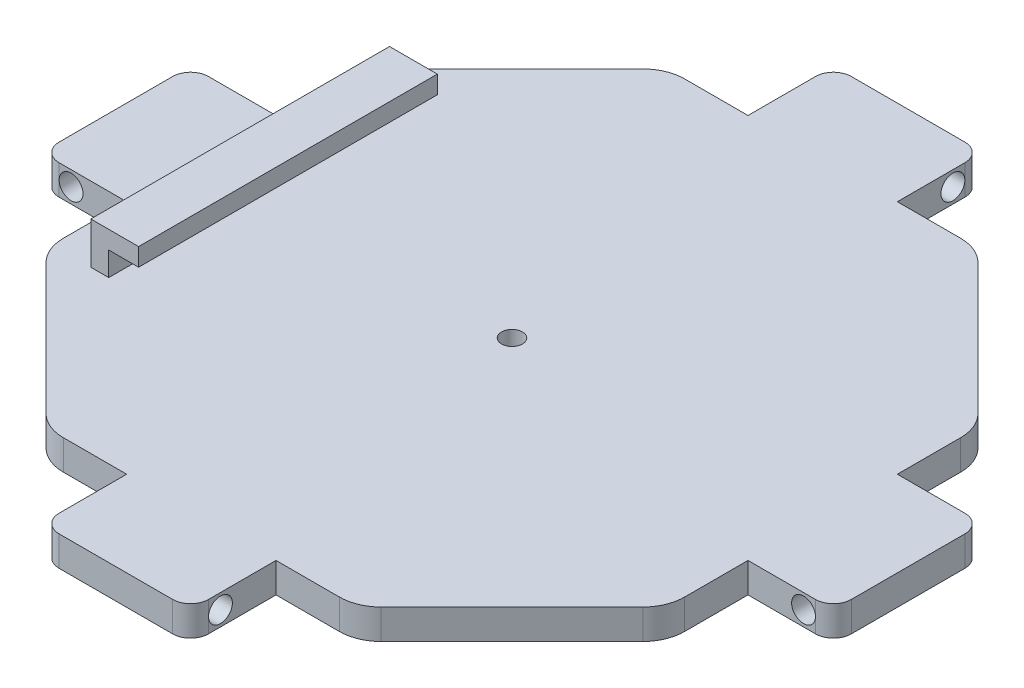
SolidWorks part; units mm, degrees
ref_plane "정면" through (0, 0, 0) normal (0, 0, 1) x (1, 0, 0)
ref_plane "윗면" through (0, 0, 0) normal (0, 1, 0) x (1, 0, 0)
ref_plane "우측면" through (0, 0, 0) normal (1, 0, 0) x (0, 0, -1)
sketch "스케치1" plane through (0, 0, 0) normal (0, 1, 0) x (1, 0, 0)
  line L0 (0, 0) -> (-27.1519, 0) construction
  line L1 (-39, 39) -> (39, 39)
  line L2 (-39, 39) -> (-39, -39)
  line L3 (-39, -39) -> (39, -39)
  line L4 (39, 39) -> (39, -39)
  line L5 (-39, 39) -> (39, -39) construction
  line L6 (-39, -39) -> (39, 39) construction
  line L7 (39, 0) -> (-66.3, 0) construction
  line L8 (-66.3, 0) -> (0, 39) construction
  line L9 (0, 39) -> (0, -39) construction
  line L10 (-26, 39) -> (-39, 26)
  line L11 (-39, -26) -> (-26, -39)
  line L12 (26, -39) -> (39, -26)
  line L13 (26, 39) -> (39, 26)
  line L14 (-26, -52) -> (26, -52)
  line L15 (26, -52) -> (52, -26)
  line L16 (52, -26) -> (52, 26)
  line L17 (52, 26) -> (26, 52)
  line L18 (26, 52) -> (-26, 52)
  line L19 (-26, 52) -> (-52, 26)
  line L20 (-52, 26) -> (-52, -26)
  line L21 (-52, -26) -> (-26, -52)
  line L22 (-52, 12.5) -> (-66.3, 12.5)
  line L23 (-66.3, 12.5) -> (-66.3, -12.5)
  line L24 (-66.3, -12.5) -> (-52, -12.5)
  line L25 (-12.5, -52) -> (-12.5, -66.3)
  line L26 (-12.5, -66.3) -> (12.5, -66.3)
  line L27 (12.5, -66.3) -> (12.5, -52)
  line L28 (52, -12.5) -> (66.3, -12.5)
  line L29 (66.3, -12.5) -> (66.3, 12.5)
  line L30 (66.3, 12.5) -> (52, 12.5)
  line L31 (-12.5, 52) -> (-12.5, 66.3)
  line L32 (-12.5, 66.3) -> (12.5, 66.3)
  line L33 (12.5, 66.3) -> (12.5, 52)
  point P0 (0, 0)
  dimension "D1" = 78
  dimension "D2" = 78
  dimension "D3" = 26
  dimension "D4" = 26
  dimension "D5" = 26
  dimension "D6" = 26
  dimension "D7" = 26
  dimension "D8" = 26
  dimension "D9" = 26
  dimension "D10" = 26
  dimension "D11" = 13
  dimension "D12" = 13
  dimension "D13" = 13
  dimension "D14" = 13
  dimension "D15" = 25
  dimension "D16" = 25
  dimension "D17" = 25
  dimension "D18" = 25
  dimension "D19" = 14.3
  dimension "D20" = 14.3
  dimension "D21" = 14.3
  dimension "D22" = 14.3
  dimension "D23" = 14.3
  dimension "D24" = 12.5
  dimension "D25" = 12.5
  dimension "D26" = 12.5
extrude "보스-돌출1" add sketch "스케치1" along normal blind 5 contours L18 L19 L1 L17 | L10 L1 L2 | L20 L21 L2 L19 | L23 L24 L20 L22 | L33 L32 L31 L18 | L1 L13 L4 | L16 L17 L4 L15 | L29 L30 L16 L28 | L12 L3 L4 | L3 L21 L14 L15 | L11 L2 L3 | L26 L27 L14 L25 region at (0, 0, -45.0667) region at (-34.6667, 0, -34.6667) region at (-45.0667, 0, 0) region at (34.6667, 0, -34.6667) region at (-34.6667, 0, 34.6667) region at (0, 0, -59.15) region at (-59.15, 0, 0) region at (45.0667, 0, 0) region at (0, 0, 45.0667) region at (34.6667, 0, 34.6667) region at (59.15, 0, 0) region at (0, 0, 59.15)
fillet "필렛1" radius 3 8 edges at (-12.5, 2.5, 66.3) (66.3, 2.5, 12.5) (66.3, 2.5, -12.5) (12.5, 2.5, -66.3) (-12.5, 2.5, -66.3) (-66.3, 2.5, -12.5) (-66.3, 2.5, 12.5) (12.5, 2.5, 66.3)
fillet "필렛2" radius 7 8 edges at (26, 2.5, -52) (52, 2.5, -26) (52, 2.5, 26) (26, 2.5, 52) (-26, 2.5, 52) (-52, 2.5, 26) (-52, 2.5, -26) (-26, 2.5, -52)
fillet "필렛3" radius 23 8 edges at (-39, 2.5, 26) (-26, 2.5, 39) (26, 2.5, 39) (39, 2.5, 26) (39, 2.5, -26) (26, 2.5, -39) (-26, 2.5, -39) (-39, 2.5, -26)
sketch "스케치6" plane through (0, 5, 0) normal (0, 1, 0) x (1, 0, 0)
  line L0 (-39, 16.4731) -> (-39, -16.4731) construction
  line L5 (16.4731, 39) -> (-16.4731, 39)
  line L6 (-39, 16.4731) -> (-39, -16.4731)
  line L7 (-16.4731, -39) -> (16.4731, -39)
  line L8 (39, -16.4731) -> (39, 16.4731)
  arc A0 (16.4731, 39) -> (32.4983, 32.4983) centre (16.4731, 16) cw
  arc A1 (32.4983, 32.4983) -> (39, 16.4731) centre (16, 16.4731) cw
  arc A2 (32.4983, -32.4983) -> (39, -16.4731) centre (16, -16.4731) ccw
  arc A3 (32.4983, -32.4983) -> (16.4731, -39) centre (16.4731, -16) cw
  arc A4 (-32.4983, -32.4983) -> (-16.4731, -39) centre (-16.4731, -16) ccw
  arc A5 (-32.4983, -32.4983) -> (-39, -16.4731) centre (-16, -16.4731) cw
  arc A6 (-32.4983, 32.4983) -> (-39, 16.4731) centre (-16, 16.4731) ccw
  arc A7 (-32.4983, 32.4983) -> (-39, 16.4731) centre (-16, 16.4731) ccw construction
  arc A8 (-32.4983, 32.4983) -> (-16.4731, 39) centre (-16.4731, 16) cw
extrude "보스-돌출2" add sketch "스케치6" against normal blind 5
sketch "스케치7" plane through (0, 5, 0) normal (0, 1, 0) x (1, 0, 0)
  circle A0 centre (0, 0) radius 1.75
  dimension "D1" = 3.5
extrude "컷-돌출5" cut sketch "스케치7" against normal through all
sketch "스케치8" plane through (0, 5, 0) normal (0, 1, 0) x (1, 0, 0)
  line L0 (28.0503, -49.9497) -> (49.9497, -28.0503) construction
  line L1 (-39, 39) -> (39, 39)
  line L2 (-39, 39) -> (-39, -39)
  line L3 (-39, -39) -> (39, -39)
  line L4 (39, 39) -> (39, -39)
  line L5 (-39, 39) -> (39, -39) construction
  line L6 (-39, -39) -> (39, 39) construction
  point P0 (0, 0)
sketch "스케치9" plane through (0, 5, 0) normal (0, 1, 0) x (1, 0, 0)
  line L0 (108.4856, 0) -> (-108.4856, 0) construction
  line L1 (-45.5, 25) -> (-42.5, 25)
  line L2 (-45.5, 25) -> (-45.5, -25)
  line L4 (-42.5, 25) -> (-42.5, -25)
  line L5 (-45.5, -25) -> (-42.5, -25)
  dimension "D1" = 42.5
  dimension "D2" = 3
extrude "보스-돌출3" add sketch "스케치9" along normal blind 7
sketch "스케치10" plane through (-42.5, 0, 0) normal (1, 0, 0) x (0, 0, -1)
  line L0 (-25, 12) -> (-25, 5) construction
  line L1 (25, 12) -> (-25, 12)
  line L2 (25, 12) -> (25, 9)
  line L3 (25, 9) -> (-25, 9)
  line L4 (-25, 12) -> (-25, 9)
  dimension "D1" = 3
extrude "보스-돌출4" add sketch "스케치10" along normal blind 5
sketch "스케치11" plane through (0, 0, 12.5) normal (0, 0, 1) x (1, 0, 0)
  line L0 (-66.3, 0) -> (-66.3, 5) construction
  line L1 (-63.3, 5) -> (-52, 5) construction
  line L2 (66.3, 5) -> (66.3, 0) construction
  line L3 (52, 5) -> (63.3, 5) construction
  circle A0 centre (-61.3, 2.5) radius 2
  circle A1 centre (61.3, 2.5) radius 2
  dimension "D1" = 4
  dimension "D6" = 4
  dimension "D2" = 5
  dimension "D3" = 2.5
  dimension "D4" = 5
  dimension "D5" = 2.5
extrude "컷-돌출6" cut sketch "스케치11" against normal through all
sketch "스케치12" plane through (-12.5, 0, 0) normal (-1, 0, 0) x (0, 0, 1)
  line L0 (-66.3, 0) -> (-66.3, 5) construction
  line L1 (-52, 5) -> (-63.3, 5) construction
  line L2 (66.3, 5) -> (66.3, 0) construction
  circle A0 centre (-61.3, 2.5) radius 2
  circle A1 centre (61.3, 2.5) radius 2
  dimension "D3" = 4
  dimension "D4" = 4
  dimension "D1" = 5
  dimension "D2" = 2.5
  dimension "D5" = 5
extrude "컷-돌출7" cut sketch "스케치12" against normal through all
